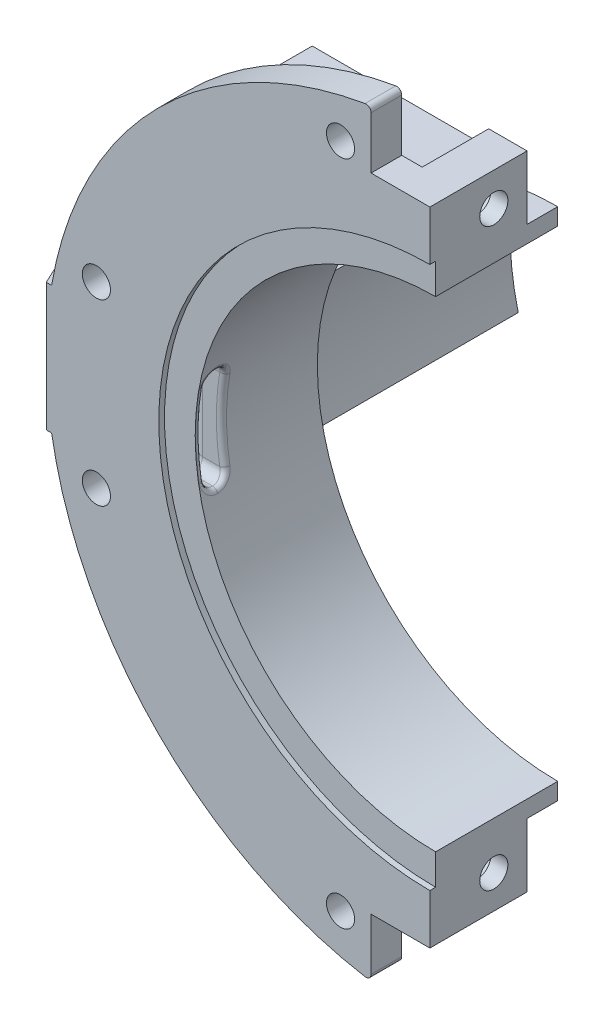
SolidWorks part; units mm, degrees
ref_plane "Front" through (0, 0, 0) normal (0, 0, 1) x (1, 0, 0)
ref_plane "Top" through (0, 0, 0) normal (0, 1, 0) x (1, 0, 0)
ref_plane "Right" through (0, 0, 0) normal (1, 0, 0) x (0, 0, -1)
sketch "Sketch1" plane through (0, 0, 0) normal (0, 0, 1) x (1, 0, 0)
  line L1 (0, 0) -> (180, 0)
  line L2 (0, 0) -> (0, 180)
  line L3 (0, 180) -> (180, 180)
  line L4 (180, 0) -> (180, 180)
  dimension "D1" = 180
extrude "Boss-Extrude1" add sketch "Sketch1" along normal blind 6
sketch "Sketch2" plane through (0, 0, 0) normal (0, 0, -1) x (-1, 0, 0)
  line L0 (0, 90) -> (-180, 90) construction
  line L1 (0, 180) -> (0, 0) construction
  line L3 (-180, 0) -> (-180, 180) construction
  circle A0 centre (-90, 90) radius 46.3
  circle A1 centre (-90, 90) radius 50.3
  point P11 (-90, 90)
  dimension "D1" = 92.6
  dimension "D2" = 4
extrude "Boss-Extrude2" add sketch "Sketch2" along normal blind 19
sketch "Sketch3" plane through (0, 0, 0) normal (0, 0, -1) x (-1, 0, 0)
  circle A0 centre (-90, 90) radius 47
  dimension "D1" = 94
extrude "Cut-Extrude1" cut sketch "Sketch3" against normal through all both and the other way through all
sketch "Sketch4" plane through (0, 0, 0) normal (0, 0, -1) x (-1, 0, 0)
  line L0 (0, 77.5) -> (0, 102.5)
  line L1 (0, 180) -> (0, 0) construction
  line L2 (0, 77.5) -> (-41.2779, 77.5)
  line L3 (0, 102.5) -> (-41.2779, 102.5)
  circle A0 centre (-90, 90) radius 50.3 construction
  arc A1 (-41.2779, 77.5) -> (-41.2779, 102.5) centre (-90, 90) ccw
  point P2 (0, 90)
  point P5 (0, 90)
  dimension "D1" = 25
extrude "Boss-Extrude3" add sketch "Sketch4" along normal blind 60
ref_plane "Plane1" through (0, 90, 0) normal (0, -1, 0) x (-1, 0, 0)
sketch "Sketch6" plane through (0, 90, 0) normal (0, -1, 0) x (-1, 0, 0)
  line L0 (-51.2779, -3.75) -> (-40, -3.75)
  line L1 (-40, -3.75) -> (-4, 21.25)
  line L2 (-51.2779, 0.25) -> (-37.2779, 0.25)
  line L3 (-37.2779, 60) -> (-37.2779, 0.25)
  line L4 (-51.2779, 0.25) -> (-51.2779, -3.75)
  line L5 (-4, 21.25) -> (-4, 60)
  line L6 (-41.2779, 60) -> (0, 60) construction
  line L7 (-4, 60) -> (-37.2779, 60)
  line L8 (0, 60) -> (0, 0) construction
  line L9 (-41.2779, 60) -> (-41.2779, 19) construction
  line L11 (-137, -6) -> (-43, -6) construction
  dimension "D1" = 4
  dimension "D2" = 4
  dimension "D3" = 4
  dimension "D4" = 6.25
  dimension "D5" = 36
  dimension "D6" = 14
  dimension "D7" = 25
extrude "Cut-Extrude2" cut sketch "Sketch6" against normal mid plane 20
fillet "Fillet2" radius 5 2 edges at (4, 90, -21.25) (40, 90, 3.75)
fillet "Fillet3" radius 2 15 edges at (22.4309, 100, -8.4507) (40.0716, 100, 3.5215) (22.4309, 80, -8.4507) (40.0716, 80, 3.5215) (40.677, 80, -0.25) (40.677, 100, -0.25) (42.821, 100, 3.75) (42.821, 80, 3.75) (4, 100, -41.9326) (4.5694, 100, -21.5478) (4, 80, -41.9326) (4.5694, 80, -21.5478) (37.2779, 100, -30.125) (37.2779, 80, -30.125) (37.2779, 90, -0.25)
fillet "Fillet4" radius 3 2 edges at (41.2779, 77.5, -9.5) (41.2779, 102.5, -9.5)
hole_wizard "M5 Clearance Hole1" positions "Sketch11" profile "Sketch12" hole size "M5" standard "ANSI Metric" end condition up to next
sketch "Sketch11" plane through (0, 0, 0) normal (0, 0, -1) x (-1, 0, 0)
  point P52 (-107.4703, 155.2)
  point P58 (-155.2, 107.4703)
  point P61 (-155.2, 72.5297)
  point P67 (-107.4703, 24.8)
  point P70 (-72.5297, 24.8)
  point P76 (-24.8, 72.5297)
  point P79 (-24.8, 107.4703)
  point P85 (-72.5297, 155.2)
sketch "Sketch12" plane through (107.4703, 155.2, 0) normal (1, 0, 0) x (0, 1, 0)
  line L0 (0, 0) -> (0, 6)
  line L1 (0, 6) -> (2.75, 6)
  line L2 (2.75, 6) -> (2.75, 0)
  line L5 (2.75, 0) -> (0, 0)
  line L11 (0, -6.35) -> (0, 107.95) construction
  dimension "Thru Hole Dia." = 5.5
  dimension "Thru Hole Depth" = 6
sketch "Sketch15" plane through (0, 0, 0) normal (0, 0, -1) x (-1, 0, 0)
  line L0 (-180, 90) -> (-90, 90) construction
  line L3 (-180, 0) -> (-180, 180) construction
  line L4 (-137.3, 93.5) -> (-137.3, 86.5)
  line L5 (-137.3, 93.5) -> (-162.3, 93.5)
  line L6 (-162.3, 93.5) -> (-162.3, 86.5)
  line L7 (-137.3, 86.5) -> (-162.3, 86.5)
  line L8 (-86.7828, 36.8215) -> (-86.5, 36.7) construction
  line L9 (-93.5, 36.7) -> (-94.1876, 43.4043) construction
  arc A0 (-41.8739, 104.6276) -> (-41.8739, 75.3724) centre (-90, 90) ccw construction
  point P4 (-137.3, 90)
  point P6 (-93.8226, 39.8455)
  dimension "D1" = 7
  dimension "D2" = 25
  dimension "D3" = 47.3
extrude "Boss-Extrude5" add sketch "Sketch15" along normal blind 19
ref_plane "Plane2" through (0, 90, 0) normal (0, 1, 0) x (0, 0, -1)
sketch "Sketch17" plane through (0, 90, 0) normal (0, 1, 0) x (0, 0, -1)
  line L6 (-1.0441, -134.6888) -> (19, -154.733)
  line L8 (19, -140.1781) -> (19, -162.3) construction
  line L9 (19, -154.733) -> (19, -159.233)
  line L10 (19, -159.233) -> (-5.5441, -134.6888)
  line L11 (-5.5441, -134.6888) -> (-1.0441, -134.6888)
  dimension "D1" = 4.5
  dimension "D2" = 4.5
extrude "Cut-Extrude3" cut sketch "Sketch17" against normal mid plane 4 contours L6 L9 L10 | L11 L10 L9 L6 region at (145.8738, 90, -7.8151)
fillet "Fillet5" radius 1.5 4 edges at (145.8452, 92, -10.1122) (145.8452, 88, -10.1122) (148.0952, 92, -7.8622) (148.0952, 88, -7.8622)
sketch "Sketch30" plane through (0, 90, 0) normal (0, -1, 0) x (-1, 0, 0)
  line L1 (22.1625, 78.3225) -> (-206.3555, 78.3225)
  line L2 (22.1625, 78.3225) -> (22.1625, -34.6262)
  line L3 (22.1625, -34.6262) -> (-206.3555, -34.6262)
  line L4 (-206.3555, 78.3225) -> (-206.3555, -34.6262)
sketch "Sketch31" plane through (0, 0, 6) normal (0, 0, 1) x (1, 0, 0)
  line L2 (0, 180) -> (0, 0) construction
  line L3 (0, 0) -> (180, 0) construction
  line L4 (180, 0) -> (180, 180) construction
  line L5 (180, 180) -> (0, 180) construction
  line L8 (0, 180) -> (0, 102.5)
  line L9 (0, 0) -> (180, 0)
  line L10 (180, 0) -> (180, 180)
  line L11 (180, 180) -> (0, 180)
  line L12 (0, 77.5) -> (0, 0)
  line L13 (41.2779, 77.5) -> (0, 77.5) construction
  line L14 (0, 102.5) -> (41.2779, 102.5) construction
  line L15 (16.049, 77.5) -> (0, 77.5)
  line L16 (0, 102.5) -> (16.049, 102.5)
  circle A4 centre (90, 90) radius 75 construction
  arc A5 (16.049, 77.5) -> (16.049, 102.5) centre (90, 90) ccw
extrude "Cut-Extrude4" cut sketch "Sketch31" against normal up to next contours A5 L16 L8 L11 L10 L9 L12 L15
sketch "Sketch33" plane through (0, 0, 6) normal (0, 0, 1) x (1, 0, 0)
  line L1 (0, 102.5) -> (1, 102.5)
  line L2 (0, 102.5) -> (0, 77.5)
  line L3 (0, 77.5) -> (1, 77.5)
  line L4 (1, 102.5) -> (1, 77.5)
  dimension "D1" = 1
extrude "Cut-Extrude5" cut sketch "Sketch33" against normal up to next
sketch "Sketch35" plane through (0, 0, 0) normal (0, 0, -1) x (-1, 0, 0)
  line L0 (-90, 15) -> (-90, 165) construction
  line L4 (-97.5, 152.7377) -> (-82.5, 152.7377)
  line L5 (-97.5, 152.7377) -> (-97.5, 139.7377)
  line L6 (-97.5, 139.7377) -> (-82.5, 139.7377)
  line L7 (-82.5, 152.7377) -> (-82.5, 139.7377)
  line L8 (-97.5, 40.2623) -> (-82.5, 40.2623)
  line L9 (-97.5, 40.2623) -> (-97.5, 27.2623)
  line L10 (-97.5, 27.2623) -> (-82.5, 27.2623)
  line L11 (-82.5, 40.2623) -> (-82.5, 27.2623)
  arc A0 (-16.049, 102.5) -> (-16.049, 77.5) centre (-90, 90) ccw construction
  arc A1 (-41.8739, 104.6276) -> (-140.1781, 93.5) centre (-90, 90) ccw construction
  arc A2 (-140.1781, 86.5) -> (-41.8739, 75.3724) centre (-90, 90) ccw construction
  point P8 (-90, 90)
  point P18 (-90, 152.7377)
  point P26 (-90, 27.2623)
  dimension "D1" = 15
  dimension "D2" = 13
  dimension "D3" = 13
  dimension "D4" = 15
extrude "Boss-Extrude6" add sketch "Sketch35" along normal blind 13
hole_wizard "M5 Clearance Hole2" positions "Sketch38" profile "Sketch39" hole size "M5" standard "ANSI Metric" end condition through all
sketch "Sketch38" plane through (97.5, 0, 0) normal (1, 0, 0) x (0, 0, -1)
  line L0 (13, 152.7377) -> (0, 152.7377) construction
  line L1 (13, 40.2623) -> (13, 27.2623) construction
  line L2 (13, 152.7377) -> (13, 139.7377) construction
  point P0 (6.5, 146.2377)
  point P3 (6.5, 33.7623)
  point P8 (6.5, 152.7377)
  point P12 (13, 33.7623)
  point P15 (13, 146.2377)
sketch "Sketch39" plane through (97.5, 146.2377, -6.5) normal (0, 1, 0) x (0, 0, -1)
  line L0 (0, 0) -> (0, 96.5)
  line L1 (0, 96.5) -> (2.75, 96.5)
  line L2 (2.75, 96.5) -> (2.75, 0)
  line L5 (2.75, 0) -> (0, 0)
  line L11 (0, -6.35) -> (0, 107.95) construction
  dimension "Thru Hole Dia." = 5.5
  dimension "Thru Hole Depth" = 96.5
sketch "Sketch40" plane through (82.5, 0, 0) normal (-1, 0, 0) x (0, 0, 1)
  line L0 (-13, 139.7377) -> (-13, 152.7377) construction
  line L1 (-10.5, 143.9283) -> (-6.5, 141.6189)
  line L2 (-6.5, 141.6189) -> (-2.5, 143.9283)
  line L3 (-2.5, 143.9283) -> (-2.5, 148.5471)
  line L4 (-2.5, 148.5471) -> (-6.5, 150.8565)
  line L5 (-6.5, 150.8565) -> (-10.5, 148.5471)
  line L6 (-10.5, 148.5471) -> (-10.5, 143.9283)
  line L7 (-13, 27.2623) -> (-13, 139.7377) construction
  line L8 (-2.5, 31.4529) -> (-2.5, 36.0717)
  line L9 (-2.5, 36.0717) -> (-6.5, 38.3811)
  line L10 (-6.5, 38.3811) -> (-10.5, 36.0717)
  line L11 (-10.5, 36.0717) -> (-10.5, 31.4529)
  line L12 (-10.5, 31.4529) -> (-6.5, 29.1435)
  line L13 (-6.5, 29.1435) -> (-2.5, 31.4529)
  circle A0 centre (-6.5, 146.2377) radius 4 construction
  circle A1 centre (-6.5, 33.7623) radius 4 construction
  dimension "D1" = 8
  dimension "D2" = 8
extrude "Cut-Extrude6" cut sketch "Sketch40" against normal blind 4.2
sketch "Sketch41" plane through (0, 0, 0) normal (0, 0, -1) x (-1, 0, 0)
  line L0 (-90, 15) -> (-90, 165) construction
  line L2 (22.1625, 90) -> (-206.3555, 90) construction
  line L3 (-101.5, 152.7377) -> (-78.5, 152.7377)
  line L4 (-101.5, 152.7377) -> (-101.5, 167.7377)
  line L5 (-101.5, 167.7377) -> (-78.5, 167.7377)
  line L6 (-78.5, 152.7377) -> (-78.5, 167.7377)
  line L7 (-165, 90) -> (-15, 90) construction
  line L8 (-78.5, 27.2623) -> (-78.5, 12.2623)
  line L9 (-101.5, 12.2623) -> (-78.5, 12.2623)
  line L10 (-101.5, 27.2623) -> (-101.5, 12.2623)
  line L11 (-101.5, 27.2623) -> (-78.5, 27.2623)
  line L14 (-82.5, 152.7377) -> (-97.5, 152.7377) construction
  arc A0 (-16.049, 102.5) -> (-16.049, 77.5) centre (-90, 90) ccw construction
  arc A1 (-16.049, 102.5) -> (-16.049, 77.5) centre (-90, 90) ccw construction
  point P3 (0, 0)
  point P7 (-90, 90)
  point P15 (-90, 152.7377)
  point P21 (0, 0)
  point P24 (-90, 90)
  dimension "D1" = 15
  dimension "D2" = 23
extrude "Cut-Extrude7" cut sketch "Sketch41" against normal up to next
fillet "Fillet8" radius 1 4 edges at (101.5, 164.1131, 3) (78.5, 164.1131, 3) (101.5, 15.8869, 3) (78.5, 15.8869, 3)
sketch "Sketch42" plane through (0, 102.5, 0) normal (0, 1, 0) x (1, 0, 0)
  line L0 (15, -6) -> (1, 24)
  line L1 (165, -6) -> (15, -6) construction
  line L2 (1, -6) -> (16.049, -6) construction
  line L3 (1, 60) -> (1, -6) construction
  line L4 (1, 24) -> (1, -6)
  line L5 (1, -6) -> (15, -6)
  dimension "D1" = 30
  dimension "D2" = 14
extrude "Cut-Extrude8" cut sketch "Sketch42" against normal up to next
ref_plane "Plane3" through (90, 0, 0) normal (1, 0, 0) x (0, 0, -1)
sketch "Sketch43" plane through (90, 0, 0) normal (1, 0, 0) x (0, 0, -1)
  line L1 (-26.2287, 173.6103) -> (66.8607, 173.6103)
  line L2 (-26.2287, 173.6103) -> (-26.2287, 11.2507)
  line L3 (-26.2287, 11.2507) -> (66.8607, 11.2507)
  line L4 (66.8607, 173.6103) -> (66.8607, 11.2507)
sketch "Sketch46" plane through (0, 0, 0) normal (0, 0, -1) x (-1, 0, 0)
  line L0 (-101.5, 162.9366) -> (-101.5, 172.9366)
  line L1 (-101.5, 172.9366) -> (-111.5, 172.9366)
  line L2 (-111.5, 172.9366) -> (-111.5, 161.8523)
  line L9 (-101.5, 152.7377) -> (-101.5, 162.9366)
  line L13 (-140.1781, 86.5) -> (-162.3, 86.5)
  line L14 (-101.5, 152.7377) -> (-101.5, 162.9366)
  line L15 (-162.3, 93.5) -> (-140.1781, 93.5)
  line L17 (-101.5, 17.0634) -> (-101.5, 27.2623)
  line L22 (-140.1781, 86.5) -> (-162.3, 86.5)
  line L24 (-162.3, 93.5) -> (-140.1781, 93.5)
  line L35 (-101.5, 17.0634) -> (-101.5, 27.2623)
  line L36 (-101.5, 27.2623) -> (-97.5, 27.2623)
  line L37 (-101.5, 27.2623) -> (-97.5, 27.2623)
  line L38 (-97.5, 27.2623) -> (-97.5, 40.2623)
  line L40 (-97.5, 27.2623) -> (-97.5, 40.2623)
  line L42 (-162.3, 86.5) -> (-162.3, 93.5)
  line L44 (-162.3, 86.5) -> (-162.3, 93.5)
  line L46 (-97.5, 139.7377) -> (-97.5, 152.7377)
  line L48 (-97.5, 139.7377) -> (-97.5, 152.7377)
  line L50 (-97.5, 152.7377) -> (-101.5, 152.7377)
  line L52 (-97.5, 152.7377) -> (-101.5, 152.7377)
  arc A16 (-101.5, 162.9366) -> (-102.6689, 163.9222) centre (-102.5, 162.9366) ccw
  arc A18 (-101.5, 162.9366) -> (-102.6689, 163.9222) centre (-102.5, 162.9366) ccw
  arc A25 (-102.6689, 163.9222) -> (-102.6689, 16.0778) centre (-90, 90) ccw
  arc A26 (-102.6689, 163.9222) -> (-102.6689, 16.0778) centre (-90, 90) ccw
  arc A27 (-102.6689, 16.0778) -> (-101.5, 17.0634) centre (-102.5, 17.0634) ccw
  arc A28 (-102.6689, 16.0778) -> (-101.5, 17.0634) centre (-102.5, 17.0634) ccw
  arc A29 (-140.1781, 86.5) -> (-97.5, 40.2623) centre (-90, 90) ccw
  arc A30 (-140.1781, 86.5) -> (-97.5, 40.2623) centre (-90, 90) ccw
  arc A31 (-97.5, 139.7377) -> (-140.1781, 93.5) centre (-90, 90) ccw
  arc A32 (-97.5, 139.7377) -> (-140.1781, 93.5) centre (-90, 90) ccw
  arc M18 (-101.5, 162.9366) -> (-102.6689, 163.9222) centre (-102.5, 162.9366) ccw
  arc M19 (-102.6689, 163.9222) -> (-102.6689, 16.0778) centre (-90, 90) ccw
  dimension "D2" = 10
  dimension "D3" = 10
  dimension "D1" = 0
extrude "Boss-Extrude8" [suppressed] add sketch "Sketch46" against normal up to surface (6 mm away) contours L1 L2 L0 M19 M18 up to face at (74.0539, 90, 6)
ref_plane "Plane5" [suppressed] through (90, 0, 0) normal (1, 0, 0) x (0, 0, -1)
mirror "Mirror2" [suppressed] about plane through (90, 0, 0) normal (1, 0, 0)
ref_plane "Plane4" [suppressed] through (0, 90, 0) normal (0, 1, 0) x (1, 0, 0)
mirror "Mirror1" [suppressed] about plane through (0, 90, 0) normal (0, 1, 0)
fillet "Fillet10" [suppressed] radius 1
sketch "Sketch47" plane through (0, 0, 6) normal (0, 0, 1) x (1, 0, 0)
  circle A0 centre (90, 90) radius 53
  circle A1 centre (90, 90) radius 47 construction
  point P3 (0, 0)
  dimension "D1" = 106
extrude "Cut-Extrude10" cut sketch "Sketch47" against normal blind 1.12
ref_plane "Plane6" through (0, 0, -5) normal (0, 0, 1) x (1, 0, 0)
fillet "Fillet12" radius 1 6 edges at (43.9862, 99.5778, 0.521) (43.9224, 99.2656, 3.2986) (43, 90, 3.75) (43.9862, 80.4222, 2.979) (43.9224, 80.7344, 0.2014) (43, 90, -0.25)
sketch "Sketch51" plane through (0, 0, -13) normal (0, 0, -1) x (-1, 0, 0)
  line L0 (-82.5, 152.7377) -> (-97.5, 152.7377) construction
  line L1 (-90, 190) -> (-180, 190)
  line L2 (-90, 190) -> (-90, -10)
  line L3 (-90, -10) -> (-180, -10)
  line L4 (-180, 190) -> (-180, -10)
  line L5 (-162.3, 93.5) -> (-162.3, 86.5) construction
  point P6 (-90, 152.7377)
  point P7 (-162.3, 90)
  point P10 (-180, 90)
  dimension "D1" = 90
  dimension "D2" = 200
extrude "Cut-Extrude12" cut sketch "Sketch51" against normal through all both and the other way through all
sketch "Sketch52" plane through (0, 0, -60) normal (0, 0, -1) x (-1, 0, 0)
  line L0 (-6, 100) -> (-35.2779, 100) construction
  line L1 (-11, 100) -> (-4, 100)
  line L2 (-11, 100) -> (-11, 80)
  line L3 (-11, 80) -> (-4, 80)
  line L4 (-4, 100) -> (-4, 80)
  line L5 (-6, 80) -> (-35.2779, 80) construction
  line L6 (-1, 77.5) -> (-1, 102.5) construction
  line L8 (-4, 98) -> (-4, 82) construction
  dimension "D1" = 10
extrude "Cut-Extrude13" cut sketch "Sketch52" against normal blind 41
fillet "Fillet13" radius 2 3 edges at (4, 90, -19) (4, 80, -39.5) (4, 100, -39.5)
